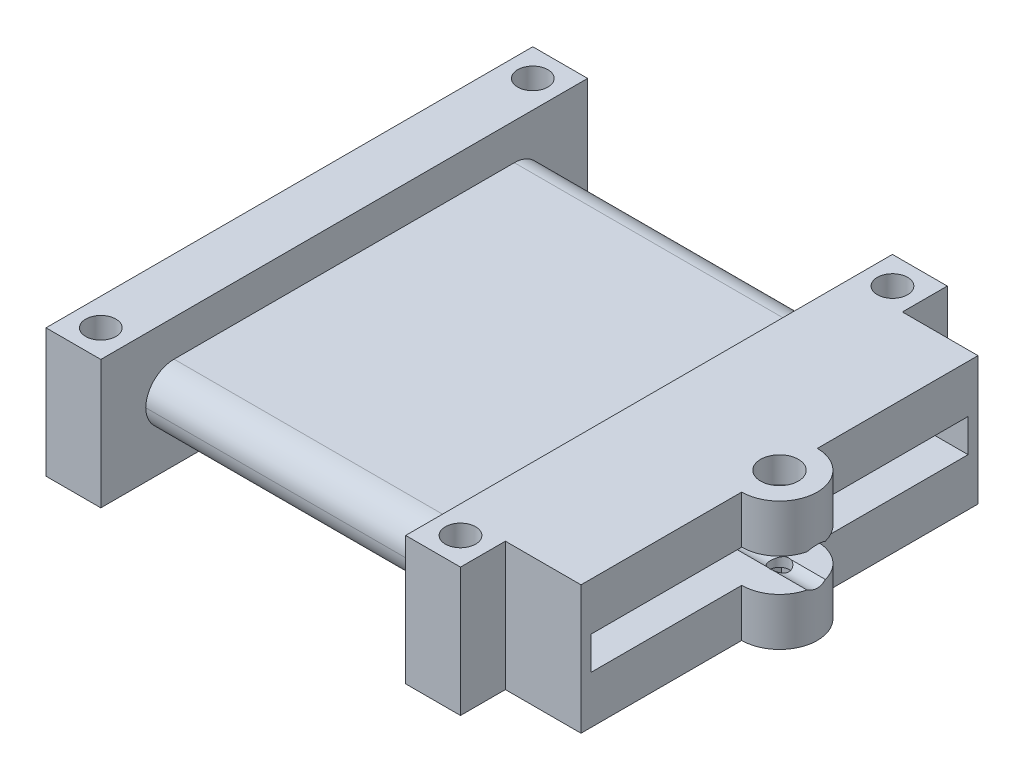
SolidWorks part; units mm, degrees
ref_plane "Front Plane" through (0, 0, 0) normal (0, 0, 1) x (1, 0, 0)
ref_plane "Top Plane" through (0, 0, 0) normal (0, 1, 0) x (1, 0, 0)
ref_plane "Right Plane" through (0, 0, 0) normal (1, 0, 0) x (0, 0, -1)
sketch "Sketch1" plane through (0, 0, 0) normal (1, 0, 0) x (0, 0, -1)
  line L0 (21, 5.9) -> (21, 0) construction
  line L1 (0, 0) -> (42, 0)
  line L2 (0, 0) -> (0, 5.9)
  line L3 (0, 5.9) -> (42, 5.9)
  line L4 (42, 0) -> (42, 5.9)
  line L6 (1.05, 1.2) -> (40.95, 1.2)
  line L7 (1.05, 1.2) -> (1.05, 4.7)
  line L8 (1.05, 4.7) -> (40.95, 4.7)
  line L9 (40.95, 1.2) -> (40.95, 4.7)
  line L10 (1.05, 1.2) -> (40.95, 4.7) construction
  line L11 (1.05, 4.7) -> (40.95, 1.2) construction
  point P7 (21, 2.95)
  dimension "D1" = 42
  dimension "D2" = 5.9
  dimension "D3" = 3.5
  dimension "D4" = 39.9
extrude "Boss-Extrude1" add sketch "Sketch1" along normal blind 32.25
fillet "Fillet2" radius 3 4 edges at (16.125, 0, -42) (16.125, 0, 0) (16.125, 5.9, 0) (16.125, 5.9, -42)
sketch "Sketch2" plane through (32.25, 0, 0) normal (1, 0, 0) x (0, 0, -1)
  line L0 (21, 5.9) -> (21, 0) construction
  line L1 (39, 5.9) -> (3, 5.9) construction
  line L2 (3, 0) -> (39, 0) construction
  line L4 (-4.75, -3.85) -> (46.75, -3.85)
  line L5 (-4.75, -3.85) -> (-4.75, 9.75)
  line L6 (-4.75, 9.75) -> (46.75, 9.75)
  line L7 (46.75, -3.85) -> (46.75, 9.75)
  line L8 (-4.75, -3.85) -> (46.75, 9.75) construction
  line L9 (-4.75, 9.75) -> (46.75, -3.85) construction
  line L14 (40.95, 1.2) -> (1.05, 1.2)
  line L15 (40.95, 1.2) -> (40.95, 4.7)
  line L16 (40.95, 4.7) -> (1.05, 4.7)
  line L17 (1.05, 1.2) -> (1.05, 4.7)
  line L18 (40.95, 1.2) -> (1.05, 4.7) construction
  line L19 (40.95, 4.7) -> (1.05, 1.2) construction
  point P6 (21, 2.95)
  point P11 (21, 2.95)
  point P12 (21, 2.95)
  dimension "D1" = 13.6
  dimension "D2" = 51.5
extrude "Boss-Extrude2" add sketch "Sketch2" along normal blind 5.8
sketch "Sketch3" plane through (0, 0, 0) normal (-1, 0, 0) x (0, 0, 1)
  line L0 (-21, 5.9) -> (-21, 0) construction
  line L1 (-39, 5.9) -> (-3, 5.9) construction
  line L2 (-3, 0) -> (-39, 0) construction
  line L4 (4.75, -3.85) -> (-46.75, -3.85)
  line L5 (4.75, -3.85) -> (4.75, 9.75)
  line L6 (4.75, 9.75) -> (-46.75, 9.75)
  line L7 (-46.75, -3.85) -> (-46.75, 9.75)
  line L8 (4.75, -3.85) -> (-46.75, 9.75) construction
  line L9 (4.75, 9.75) -> (-46.75, -3.85) construction
  line L10 (-1.05, 1.2) -> (-40.95, 1.2)
  line L11 (-1.05, 1.2) -> (-1.05, 4.7)
  line L12 (-1.05, 4.7) -> (-40.95, 4.7)
  line L13 (-40.95, 1.2) -> (-40.95, 4.7)
  line L14 (-1.05, 1.2) -> (-40.95, 4.7) construction
  line L15 (-1.05, 4.7) -> (-40.95, 1.2) construction
  point P6 (-21, 2.95)
  point P12 (-21, 2.95)
extrude "Boss-Extrude3" add sketch "Sketch3" along normal blind 5.8
sketch "Sketch4" plane through (0, 9.75, 0) normal (0, 1, 0) x (1, 0, 0)
  line L0 (-2.9, 46.75) -> (-2.9, 43.85) construction
  line L1 (-5.8, 46.75) -> (0, 46.75) construction
  line L2 (35.15, 46.75) -> (35.15, 43.85) construction
  line L3 (38.05, 46.75) -> (32.25, 46.75) construction
  line L4 (-2.9, -4.75) -> (-2.9, -1.85) construction
  line L5 (-5.8, -4.75) -> (0, -4.75) construction
  line L6 (35.15, -4.75) -> (35.15, -1.85) construction
  line L7 (38.05, -4.75) -> (32.25, -4.75) construction
  circle A0 centre (-2.9, 43.85) radius 1.6
  circle A1 centre (35.15, 43.85) radius 1.6
  circle A2 centre (-2.9, -1.85) radius 1.6
  circle A3 centre (35.15, -1.85) radius 1.6
  dimension "D2" = 3.2
  dimension "D4" = 3.2
  dimension "D6" = 3.2
  dimension "D8" = 3.2
  dimension "D1" = 2.9
  dimension "D3" = 2.9
  dimension "D5" = 2.9
  dimension "D7" = 2.9
extrude "Cut-Extrude1" cut sketch "Sketch4" against normal through all
sketch "Sketch6" plane through (38.05, 0, 0) normal (1, 0, 0) x (0, 0, -1)
  line L0 (46.75, -3.85) -> (46.75, 9.75) construction
  line L1 (-4.75, -3.85) -> (46.75, -3.85)
  line L2 (-4.75, -3.85) -> (-4.75, 3.35)
  line L3 (-4.75, 3.35) -> (46.75, 3.35)
  line L4 (46.75, -3.85) -> (46.75, 3.35)
  dimension "D1" = 7.2
extrude "Cut-Extrude2" [suppressed] cut sketch "Sketch6" against normal blind 5.8
sketch "Sketch7" plane through (-5.8, 0, 0) normal (-1, 0, 0) x (0, 0, 1)
  line L0 (4.75, -3.85) -> (4.75, 9.75) construction
  line L1 (-46.75, -3.85) -> (4.75, -3.85)
  line L2 (-46.75, -3.85) -> (-46.75, 3.35)
  line L3 (-46.75, 3.35) -> (4.75, 3.35)
  line L4 (4.75, -3.85) -> (4.75, 3.35)
  dimension "D1" = 7.2
extrude "Cut-Extrude3" [suppressed] cut sketch "Sketch7" against normal blind 5.8
sketch "Sketch8" plane through (0, 9.75, 0) normal (0, 1, 0) x (1, 0, 0)
  line L1 (0, 41.9996) -> (32.25, 41.9996) construction
  line L2 (38.05, 46.75) -> (38.05, -4.75) construction
  line L3 (46.05, 25) -> (46.05, 41.9996)
  line L4 (46.05, 41.9996) -> (38.05, 41.9996)
  line L5 (46.05, 17) -> (46.05, 0.0004)
  line L6 (46.05, 0.0004) -> (38.05, 0.0004)
  line L12 (-42.1211, 21) -> (79.5205, 21) construction
  line L13 (-5.8, -4.75) -> (-5.8, 46.75) construction
  circle A0 centre (46.05, 21) radius 4
  point P17 (-5.8, 21)
  dimension "D1" = 8
  dimension "D2" = 8
extrude "Boss-Extrude4" add sketch "Sketch8" against normal blind 13.6
hole_wizard "CSK for M2 Flat Head Machine Screw1" positions "Sketch12" profile "Sketch13" countersink size "M2" standard "ANSI Metric" end condition through all
sketch "Sketch12" plane through (0, 9.75, 0) normal (0, 1, 0) x (1, 0, 0)
  point P0 (46.05, 21)
sketch "Sketch13" plane through (46.05, 9.75, -21) normal (1, 0, 0) x (0, 0, 1)
  line L0 (0, 0) -> (0, 13.6)
  line L1 (0, 13.6) -> (1, 13.6)
  line L2 (1, 13.6) -> (1, 3.75)
  line L3 (1, 3.75) -> (2, 2.75)
  line L4 (2, 2.75) -> (2, 0)
  line L6 (2, 0) -> (0, 0)
  line L7 (-1, 3.75) -> (-2, 2.75) construction
  line L11 (0, -6.35) -> (0, 107.95) construction
  dimension "Thru Hole Dia." = 2
  dimension "Thru Hole Depth" = 13.6
  dimension "C'Sink Dia." = 4
  dimension "C'Sink Angle" = 90
  dimension "Head Clearance" = 2.75
sketch "Sketch14" plane through (0, -3.85, 0) normal (0, -1, 0) x (1, 0, 0)
  line L1 (43.6716, -20.5274) -> (44.4516, -22.8234)
  line L2 (44.4516, -22.8234) -> (46.8299, -23.296)
  line L3 (46.8299, -23.296) -> (48.4284, -21.4726)
  line L4 (48.4284, -21.4726) -> (47.6484, -19.1766)
  line L5 (47.6484, -19.1766) -> (45.2701, -18.704)
  line L6 (45.2701, -18.704) -> (43.6716, -20.5274)
  circle A0 centre (46.05, -21) radius 2.1 construction
  dimension "D1" = 4.2
extrude "Cut-Extrude4" cut sketch "Sketch14" against normal blind 4
sketch "Sketch15" plane through (-5.8, 0, 0) normal (-1, 0, 0) x (0, 0, 1)
  line L1 (-40.95, 1.2) -> (-1.05, 1.2)
  line L2 (-40.95, 1.2) -> (-40.95, 4.7)
  line L3 (-40.95, 4.7) -> (-1.05, 4.7)
  line L4 (-1.05, 1.2) -> (-1.05, 4.7)
  line L5 (-46.75, -3.85) -> (-40.95, -3.85)
  line L6 (-46.75, -3.85) -> (-46.75, -1.85)
  line L7 (-46.75, -1.85) -> (-40.95, -1.85)
  line L8 (-40.95, -3.85) -> (-40.95, -1.85)
  line L9 (4.75, -3.85) -> (-1.05, -3.85)
  line L10 (4.75, -3.85) -> (4.75, -1.85)
  line L11 (4.75, -1.85) -> (-1.05, -1.85)
  line L12 (-1.05, -3.85) -> (-1.05, -1.85)
  dimension "D1" = 5.8
  dimension "D2" = 2
  dimension "D3" = 5.8
  dimension "D4" = 2
extrude "Cut-Extrude5" cut sketch "Sketch15" against normal through all contours L2 L1 L4 L3
sketch "Sketch17" plane through (-5.8, 0, 0) normal (-1, 0, 0) x (0, 0, 1)
  line L0 (-21, 4.7) -> (-21, 1.2) construction
  line L1 (-1.05, 4.7) -> (-40.95, 4.7) construction
  line L2 (-40.95, 1.2) -> (-1.05, 1.2) construction
  circle A0 centre (-21, 2.95) radius 2
  dimension "D1" = 4
extrude "Cut-Extrude6" cut sketch "Sketch17" against normal through all
